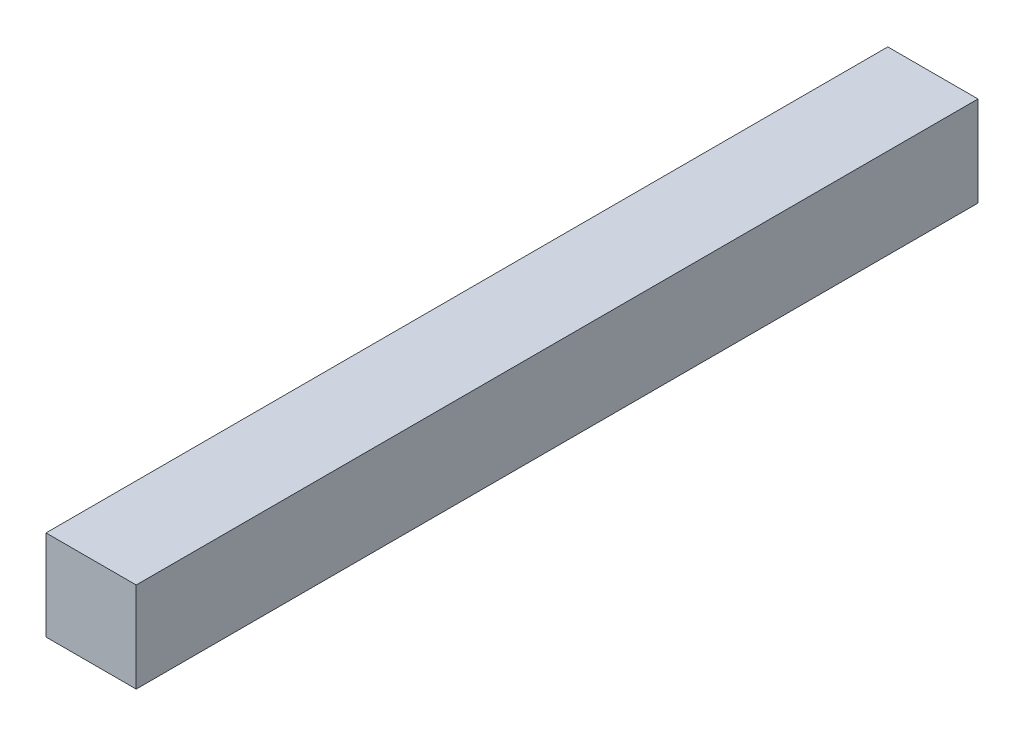
SolidWorks part; units mm, degrees
ref_plane "Front Plane" through (0, 0, 0) normal (0, 0, 1) x (1, 0, 0)
ref_plane "Top Plane" through (0, 0, 0) normal (0, 1, 0) x (1, 0, 0)
ref_plane "Right Plane" through (0, 0, 0) normal (1, 0, 0) x (0, 0, -1)
sketch "Sketch1" plane through (0, 0, 0) normal (0, 0, 1) x (1, 0, 0)
  line L0 (-1.1906, 1.1906) -> (1.1906, -1.1906) construction
  line L1 (-1.1906, 1.1906) -> (1.1906, 1.1906) construction
  line L2 (-1.1906, 1.1906) -> (-1.1906, -1.1906) construction
  line L3 (-1.1906, -1.1906) -> (1.1906, -1.1906) construction
  line L4 (1.1906, 1.1906) -> (1.1906, -1.1906) construction
  dimension "Width" = 2.3813
  dimension "Height" = 2.3813
sketch "Sketch2" plane through (0, 0, 0) normal (1, 0, 0) x (0, 0, -1)
  line L0 (152.4, 0) -> (-152.4, 0) construction
  line L1 (-145.2562, 1.1906) -> (-145.2562, -1.1906) construction
  line L2 (0, 1.1906) -> (0, -1.1906) construction
  line L3 (145.2562, -1.1906) -> (145.2562, 1.1906) construction
  line L4 (-145.2562, 0) -> (145.2562, 0) construction
  line L5 (-152.4, 0) -> (-152.4, 1.1906) construction
  line L6 (-152.4, 1.1906) -> (152.4, 1.1906) construction
  line L7 (152.4, 1.1906) -> (152.4, 0) construction
  point P2 (0, 0)
  point P3 (-145.2562, 0)
  point P5 (145.2562, 0)
  point P12 (-145.2562, 0)
  point P13 (0, 0)
  point P14 (145.2562, 0)
  dimension "D1" = 7.1437
  dimension "Length" = 304.8
sketch "Sketch3" plane through (0, 0, 0) normal (0, 0, 1) x (1, 0, 0)
  line L0 (-1.1906, 1.1906) -> (-1.1906, -1.1906)
  line L1 (-1.1906, -1.1906) -> (1.1906, -1.1906)
  line L2 (1.1906, -1.1906) -> (1.1906, 1.1906)
  line L3 (1.1906, 1.1906) -> (-1.1906, 1.1906)
extrude "Boss-Extrude1" add sketch "Sketch3" along normal blind 11.1125 and the other way blind 11.1125
